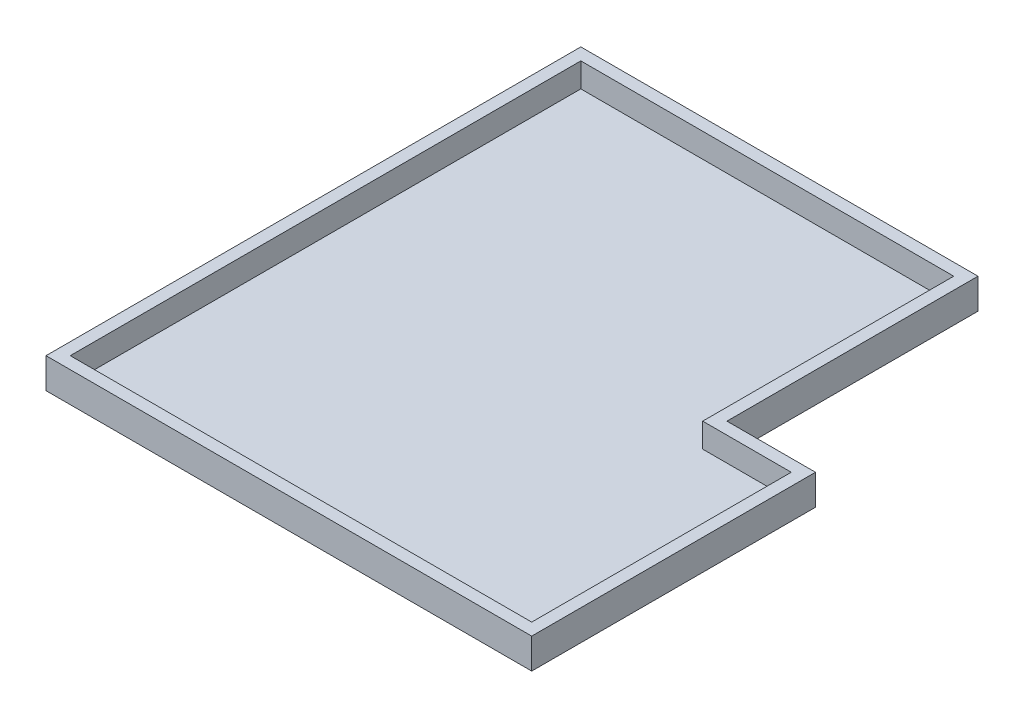
SolidWorks part; units mm, degrees
ref_plane "Front Plane" through (0, 0, 0) normal (0, 0, 1) x (1, 0, 0)
ref_plane "Top Plane" through (0, 0, 0) normal (0, 1, 0) x (1, 0, 0)
ref_plane "Right Plane" through (0, 0, 0) normal (1, 0, 0) x (0, 0, -1)
sketch "Sketch2" plane through (0, 0, 0) normal (0, 1, 0) x (1, 0, 0)
  line L1 (-1537.5, -2105) -> (1537.5, -2105)
  line L2 (-1537.5, -2105) -> (-1537.5, 2105)
  line L3 (-1537.5, 2105) -> (1537.5, 2105)
  line L4 (1537.5, 35) -> (1537.5, 2105)
  line L5 (-1537.5, -2105) -> (1537.5, 2105) construction
  line L6 (-1537.5, 2105) -> (1537.5, -2105) construction
  line L7 (1537.5, -2105) -> (2267.5, -2105)
  line L9 (1537.5, 35) -> (2267.5, 35)
  line L10 (2267.5, -2105) -> (2267.5, 35)
  line L12 (-1537.5, 2105) -> (-1537.5, -2105)
  line L14 (-1637.5, 2105) -> (-1637.5, -2105)
  line L15 (-1537.5, 2105) -> (1537.5, 2105)
  line L16 (-1637.5, 2105) -> (-1637.5, 2205)
  line L17 (-1637.5, 2205) -> (1537.5, 2205)
  line L19 (1537.5, 2205) -> (1637.5, 2205)
  line L20 (1537.5, 2105) -> (1537.5, 35)
  line L21 (1537.5, 35) -> (1637.5, 35)
  line L22 (1637.5, 2205) -> (1637.5, 135)
  line L23 (1537.5, 35) -> (2267.5, 35)
  line L24 (1537.5, 35) -> (1537.5, 135)
  line L25 (1637.5, 135) -> (2267.5, 135)
  line L26 (2267.5, 35) -> (2267.5, 101.0865)
  line L27 (-1537.5, -2105) -> (2267.5, -2105)
  line L28 (-1637.5, -2105) -> (-1637.5, -2205)
  line L29 (-1637.5, -2205) -> (2267.5, -2205)
  line L31 (2267.5, -2205) -> (2367.5, -2205)
  line L32 (2267.5, -2105) -> (2267.5, 135)
  line L33 (2267.5, 135) -> (2367.5, 135)
  line L34 (2367.5, -2205) -> (2367.5, 135)
  point P0 (0, 0)
  dimension "D1" = 3805
  dimension "D2" = 2140
  dimension "D3" = 730
  dimension "D4" = 2070
  dimension "D5" = 100
  dimension "D6" = 100
  dimension "D7" = 100
  dimension "D8" = 100
  dimension "D9" = 100
  dimension "D10" = 100
extrude "Boss-Extrude3" add sketch "Sketch2" along normal blind 50 contours L25 L22 L19 L17 L16 L14 L28 L29 L31 L34 L33
extrude "Boss-Extrude4" add sketch "Sketch2<6>" along normal blind 250 contours L31 L34 L33 L10 L7 L1 L2 L3 L20 L4 L9 L25 L22 L19 L17 L16 L14 L28 L29 region at (2317.5, 0, -75.4281)
sketch "Sketch2<6>" plane through (0, 0, 0) normal (0, 1, 0) x (1, 0, 0) same geometry as "Sketch2"
